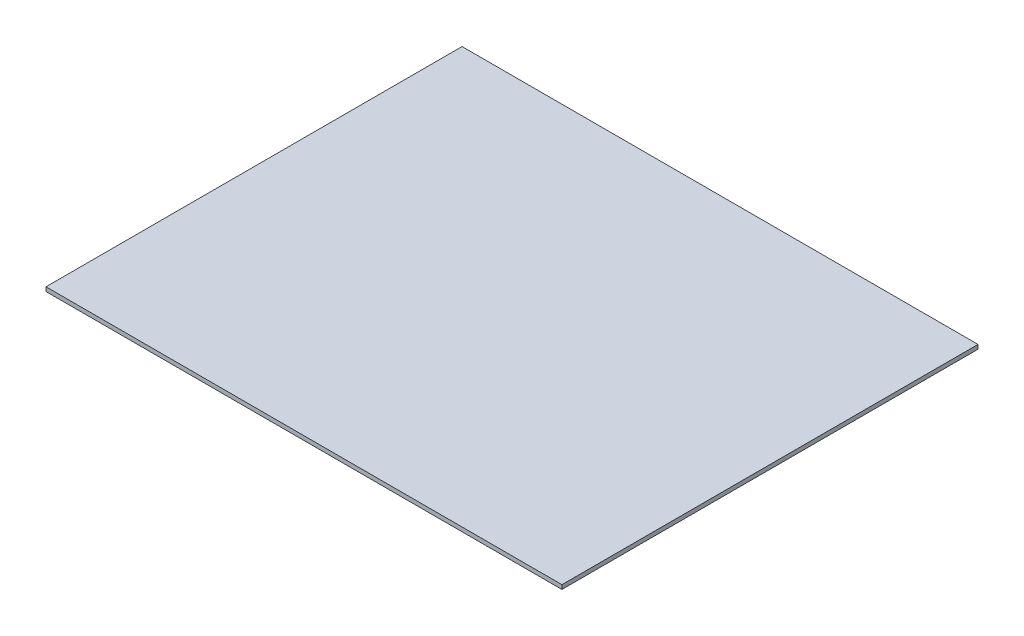
SolidWorks part; units mm, degrees
material "Acrylic (Medium-high impact)"
ref_plane "Front Plane" through (0, 0, 0) normal (0, 0, 1) x (1, 0, 0)
ref_plane "Top Plane" through (0, 0, 0) normal (0, 1, 0) x (1, 0, 0)
ref_plane "Right Plane" through (0, 0, 0) normal (1, 0, 0) x (0, 0, -1)
sketch "Sketch1" plane through (0, 0, 0) normal (0, 1, 0) x (1, 0, 0)
  line L1 (-196.85, -158.75) -> (196.85, -158.75)
  line L2 (-196.85, -158.75) -> (-196.85, 158.75)
  line L3 (-196.85, 158.75) -> (196.85, 158.75)
  line L4 (196.85, -158.75) -> (196.85, 158.75)
  line L5 (-196.85, -158.75) -> (196.85, 158.75) construction
  line L6 (-196.85, 158.75) -> (196.85, -158.75) construction
  point P0 (0, 0)
  dimension "D1" = 317.5
  dimension "D2" = 393.7
extrude "Boss-Extrude1" add sketch "Sketch1" along normal blind 3.175
